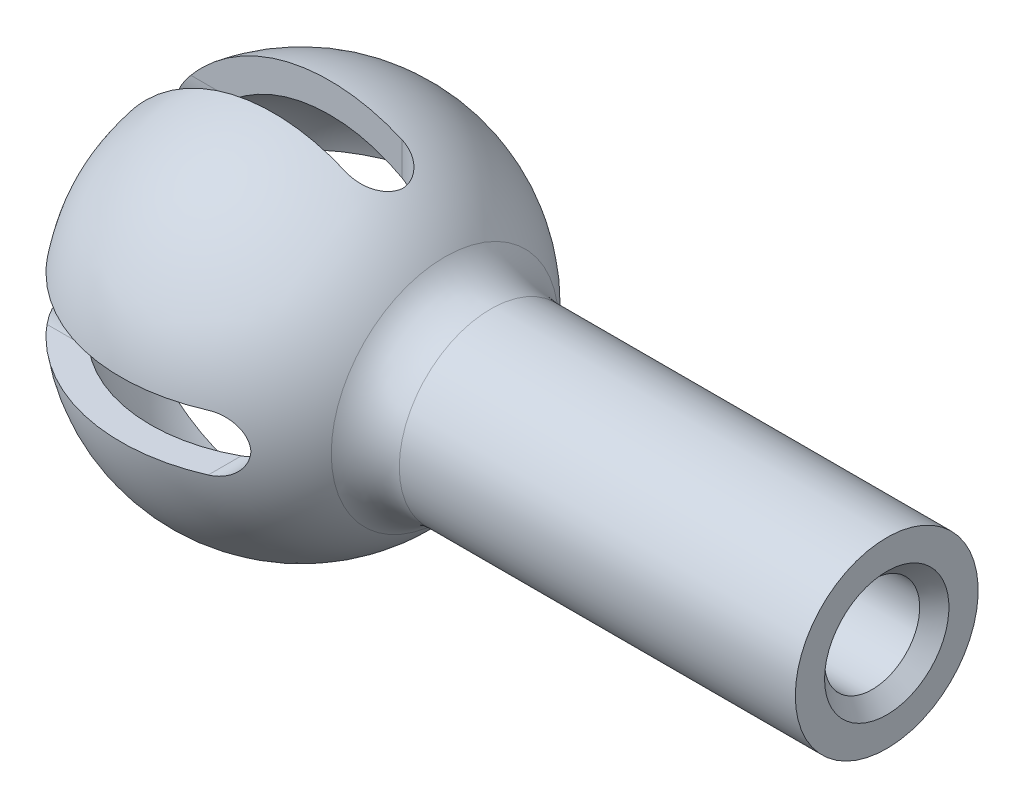
SolidWorks part; units mm, degrees
ref_plane "Front" through (0, 0, 0) normal (0, 0, 1) x (1, 0, 0)
ref_plane "Top" through (0, 0, 0) normal (0, 1, 0) x (1, 0, 0)
ref_plane "Right" through (0, 0, 0) normal (1, 0, 0) x (0, 0, -1)
sketch "Sketch1" plane through (0, 0, 0) normal (0, 0, 1) x (1, 0, 0)
  line L0 (10.5, 0) -> (48.6866, 0) construction
  line L1 (40, 6.25) -> (10.8253, 6.25)
  line L2 (40, 6.25) -> (40, 3.25)
  line L3 (40, 3.25) -> (15, 3.25)
  line L9 (15, 3.25) -> (15, 0)
  line L10 (-12.339, 2) -> (-10.3078, 2)
  line L11 (10.5, 0) -> (15, 0)
  arc A0 (10.8253, 6.25) -> (-12.339, 2) centre (0, 0) ccw
  arc A1 (10.5, 0) -> (-10.3078, 2) centre (0, 0) ccw
  point P11 (15, 0)
  dimension "D1" = 6.5
  dimension "D2" = 12.5
  dimension "D6" = 2
  dimension "D3" = 3
  dimension "D4" = 25
  dimension "D5" = 15
  dimension "D7" = 2
revolve "Revolve1" add sketch "Sketch1" angle 360 about L0
sketch "Sketch2" plane through (0, 0, 0) normal (0, 0, 1) x (1, 0, 0)
  line L1 (-15.729, 1.9156) -> (6.9395, 1.9156)
  line L2 (-15.729, 1.9156) -> (-15.729, -1.9156)
  line L3 (-15.729, -1.9156) -> (6.9395, -1.9156)
  line L4 (6.9395, 1.9156) -> (6.9395, -1.9156)
  line L5 (-15.729, 1.9156) -> (6.9395, -1.9156) construction
  line L6 (-15.729, -1.9156) -> (6.9395, 1.9156) construction
  point P0 (-4.3947, 0)
extrude "Cut-Extrude1" cut sketch "Sketch2" along normal through all
pattern_circular "CirPattern1" count 4 over 360 about axis through (10.5, 0, 0) along (-1, 0, 0) of "Cut-Extrude1" reverse direction yes
fillet "Fillet1" radius 2 8 edges at (6.9395, -1.9156, 8.9312) (6.9395, 1.9156, 8.9312) (6.9395, 1.9156, -8.9312) (6.9395, -1.9156, -8.9312) (6.9395, -8.9312, -1.9156) (6.9395, 8.9312, 1.9156) (6.9395, -8.9312, 1.9156) (6.9395, 8.9312, -1.9156)
fillet "Fillet2" radius 4 1 edges at (10.8253, 0, 6.25)
chamfer "Chamfer1" distance 1 angle 45 1 edges at (40, 0, 3.25)
fillet "Fillet3" radius 6 4 edges at (-11.1737, 1.9156, 1.9156) (-11.1737, -1.9156, 1.9156) (-11.1737, 1.9156, -1.9156) (-11.1737, -1.9156, -1.9156)
